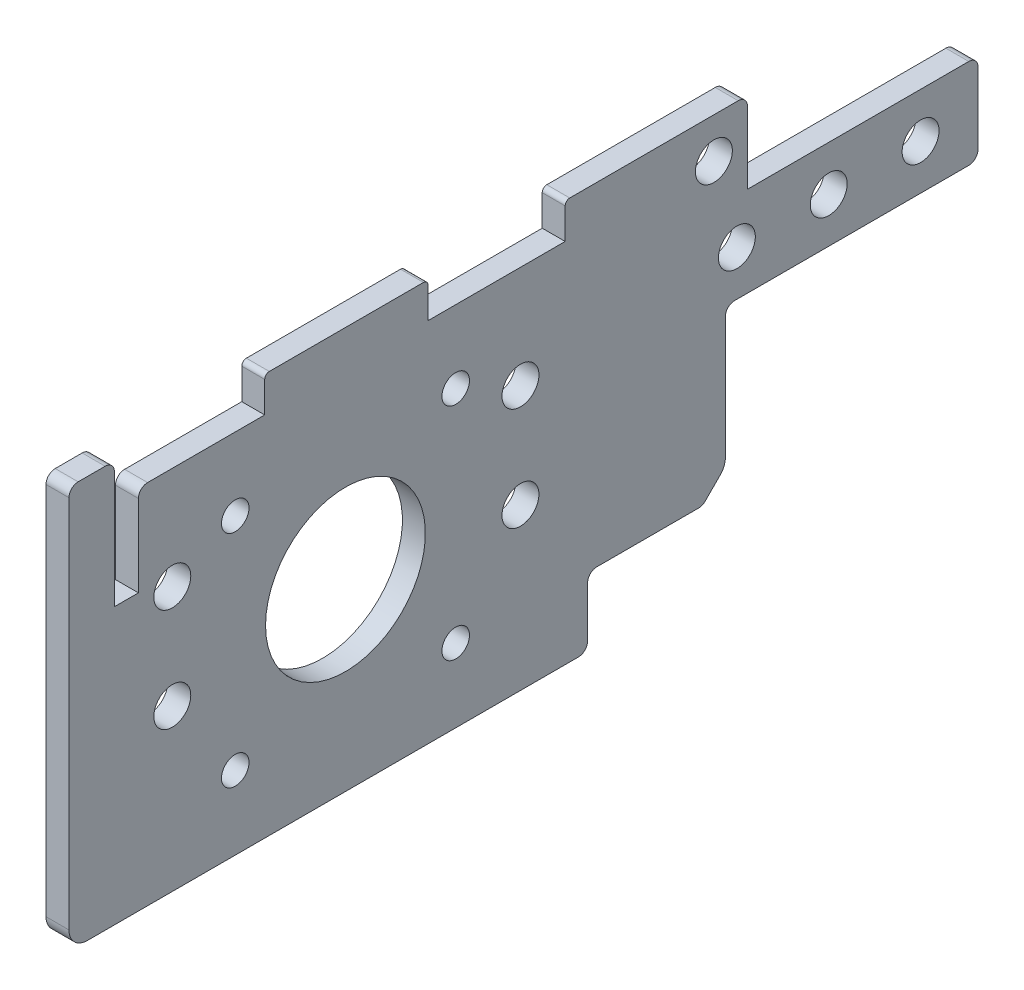
SolidWorks part; units mm, degrees
material "AISI Type A2 Tool Steel"
ref_plane "Front Plane" through (0, 0, 0) normal (0, 0, 1) x (1, 0, 0)
ref_plane "Top Plane" through (0, 0, 0) normal (0, 1, 0) x (1, 0, 0)
ref_plane "Right Plane" through (0, 0, 0) normal (1, 0, 0) x (0, 0, -1)
sketch "Top Layout" plane through (0, 0, 0) normal (0, 1, 0) x (1, 0, 0)
  line L0 (-114.046, -123.825) -> (-104.775, -123.825) construction
  line L1 (-104.775, -142.875) -> (-101.6, -142.875)
  line L2 (-104.775, -142.875) -> (-104.775, -104.775)
  line L3 (-104.775, -104.775) -> (-101.6, -104.775)
  line L4 (-101.6, -142.875) -> (-101.6, -104.775)
  line L5 (-104.775, -142.875) -> (-101.6, -104.775) construction
  line L6 (-104.775, -104.775) -> (-101.6, -142.875) construction
  line L7 (-19.05, -105.8164) -> (-101.6, -105.8164)
  line L8 (-19.05, -105.8164) -> (-19.05, -141.8336)
  line L9 (-19.05, -141.8336) -> (-101.6, -141.8336)
  line L10 (-101.6, -105.8164) -> (-101.6, -141.8336)
  line L11 (-19.05, -105.8164) -> (-101.6, -141.8336) construction
  line L12 (-19.05, -141.8336) -> (-101.6, -105.8164) construction
  line L13 (-133.096, -85.725) -> (-114.046, -85.725)
  line L14 (-133.096, -85.725) -> (-133.096, -161.925)
  line L15 (-133.096, -161.925) -> (-114.046, -161.925)
  line L16 (-114.046, -85.725) -> (-114.046, -161.925)
  line L17 (-133.096, -85.725) -> (-114.046, -161.925) construction
  line L18 (-133.096, -161.925) -> (-114.046, -85.725) construction
  line L19 (-104.775, -123.825) -> (0, -123.825) construction
  line L20 (0, -123.825) -> (0, 0) construction
  line L21 (-52.3528, -40.1717) -> (0, 0) construction
  line L22 (-70.6449, -16.3328) -> (-18.2922, 23.8388)
  line L23 (-34.0606, -64.0105) -> (18.2922, -23.8388)
  line L24 (-30.9251, 40.3023) -> (-122.2248, -29.7544)
  line L25 (-153.9748, -53.975) -> (-153.9748, -123.825)
  line L26 (-109.5248, -162.052) -> (109.5248, -162.052)
  line L27 (0, -162.052) -> (0, -123.825) construction
  line L28 (-109.5248, -162.052) -> (-109.5248, -20.0093) construction
  line L29 (-104.775, -142.875) -> (-104.775, -152.527)
  line L30 (-104.775, -152.527) -> (104.775, -152.527)
  line L31 (104.775, -104.775) -> (101.6, -104.775)
  line L32 (-144.4498, -73.025) -> (-109.5248, -73.025)
  line L33 (-144.4498, -73.025) -> (-144.4498, -123.825)
  line L34 (-144.4498, -123.825) -> (-109.5248, -123.825) construction
  line L35 (-109.5248, -73.025) -> (-109.5248, -162.052)
  line L36 (-144.4498, -73.025) -> (-109.5248, -123.825) construction
  line L37 (-144.4498, -123.825) -> (-109.5248, -73.025) construction
  line L38 (101.6, -142.875) -> (101.6, -104.775)
  line L39 (104.775, -142.875) -> (101.6, -142.875)
  line L40 (104.775, -142.875) -> (104.775, -104.775)
  line L41 (104.775, -142.875) -> (104.775, -152.527)
  line L42 (109.5248, -162.052) -> (109.5248, -20.0093) construction
  line L43 (30.9251, 40.3023) -> (122.2248, -29.7544)
  line L45 (19.05, -141.8336) -> (101.6, -141.8336)
  line L46 (101.6, -105.8164) -> (101.6, -141.8336)
  line L47 (19.05, -105.8164) -> (101.6, -105.8164)
  line L48 (19.05, -105.8164) -> (19.05, -141.8336)
  line L49 (133.096, -161.925) -> (114.046, -161.925)
  line L50 (114.046, -85.725) -> (114.046, -161.925)
  line L51 (133.096, -85.725) -> (114.046, -85.725)
  line L52 (133.096, -85.725) -> (133.096, -161.925)
  line L53 (144.4498, -123.825) -> (109.5248, -123.825) construction
  line L54 (109.5248, -73.025) -> (109.5248, -162.052)
  line L55 (144.4498, -73.025) -> (109.5248, -73.025)
  line L56 (144.4498, -73.025) -> (144.4498, -123.825)
  line L57 (-109.5248, -123.825) -> (-109.5248, -162.052) construction
  line L62 (-153.9748, -53.975) -> (-122.2248, -53.975)
  line L63 (-122.2248, -53.975) -> (-122.2248, -29.7544)
  line L64 (-144.4498, -123.825) -> (-153.9748, -123.825)
  line L65 (153.9748, -53.975) -> (153.9748, -123.825)
  line L66 (109.5248, -123.825) -> (109.5248, -162.052) construction
  line L67 (144.4498, -123.825) -> (153.9748, -123.825)
  line L68 (122.2248, -29.7544) -> (122.2248, -53.975)
  line L73 (-104.775, -104.775) -> (-104.775, -16.3647) construction
  line L74 (-95.25, -162.052) -> (-95.25, -9.0559) construction
  line L75 (-109.5248, -162.052) -> (-109.5248, -123.825) construction
  line L76 (109.5248, -162.052) -> (109.5248, -123.825) construction
  line L77 (122.2248, -53.975) -> (153.9748, -53.975)
  line L83 (104.775, -155.5496) -> (-104.775, -155.5496) construction
  line L88 (95.25, -162.052) -> (95.25, -9.0559) construction
  line L89 (104.775, -104.775) -> (104.775, -16.3647) construction
  line L92 (-104.775, -152.527) -> (-104.775, -162.052) construction
  line L93 (-14.605, -76.327) -> (14.605, -76.327)
  line L94 (-14.605, -76.327) -> (-14.605, -152.527)
  line L95 (-14.605, -152.527) -> (14.605, -152.527)
  line L96 (14.605, -76.327) -> (14.605, -152.527)
  line L97 (-14.605, -76.327) -> (14.605, -152.527) construction
  line L98 (-14.605, -152.527) -> (14.605, -76.327) construction
  line L99 (104.775, -152.527) -> (104.775, -162.052) construction
  line L100 (-19.05, -105.8164) -> (0, -105.8164) construction
  line L107 (0, -105.8164) -> (19.05, -105.8164) construction
  line L108 (104.775, -123.825) -> (114.046, -123.825) construction
  circle A0 centre (0, 0) radius 114.3
  circle A1 centre (0, 0) radius 6.35
  circle A2 centre (-52.3528, -40.1717) radius 17.8
  circle A3 centre (0, 0) radius 30.0482
  circle A4 centre (-52.3528, -40.1717) radius 30.0482
  arc A5 (-30.9251, 40.3023) -> (30.9251, 40.3023) centre (0, 0) cw
  point P2 (-103.1875, -123.825)
  point P7 (-60.325, -123.825)
  point P12 (-123.571, -123.825)
  point P30 (-126.9873, -98.425)
  point P35 (0, -114.427)
  point P53 (0, -152.527)
  dimension "D1" = 35.6
  dimension "D2" = 12.7
  dimension "D3" = 228.6
  dimension "D11" = 60.0964
  dimension "D12" = 50.8
  dimension "D14" = 52.5
  dimension "D4" = 3.175
  dimension "D5" = 19.05
  dimension "D6" = 76.2
  dimension "D7" = 82.55
  dimension "D8" = 38.1
  dimension "D9" = 104.775
  dimension "D10" = 18.0086
  dimension "D13" = 9.525
  dimension "D15" = 4.7498
  dimension "D16" = 9.525
  dimension "D17" = 9.652
  dimension "D18" = 50.8
  dimension "D19" = 12.446
  dimension "D20" = 65.9892
  dimension "D21" = 19.05
  dimension "D22" = 34.925
  dimension "D23" = 123.825
  dimension "D24" = 12.7
  dimension "D25" = 9.525
  dimension "D26" = 29.21
  dimension "D27" = 76.2
  dimension "D28" = 3.0226
sketch "Side Layout" plane through (0, 0, 0) normal (1, 0, 0) x (0, 0, -1)
  line L0 (0, -38.1) -> (0, 33.7344) construction
  line L1 (-114.3, -20.955) -> (114.3, -20.955)
  line L2 (-114.3, -20.955) -> (-114.3, -33.655)
  line L3 (-114.3, -33.655) -> (114.3, -33.655)
  line L4 (114.3, -20.955) -> (114.3, -33.655)
  line L5 (-114.3, -20.955) -> (114.3, -33.655) construction
  line L6 (-114.3, -33.655) -> (114.3, -20.955) construction
  line L7 (-9.525, -32.9406) -> (9.525, -32.9406)
  line L8 (-9.525, -32.9406) -> (-9.525, -38.1)
  line L9 (-9.525, -38.1) -> (9.525, -38.1)
  line L10 (9.525, -32.9406) -> (9.525, -38.1)
  line L11 (-9.525, -32.9406) -> (9.525, -38.1) construction
  line L12 (-9.525, -38.1) -> (9.525, -32.9406) construction
  line L13 (-11.9126, -29.3338) -> (11.9126, -29.3338)
  line L14 (-11.9126, -29.3338) -> (-11.9126, -32.9406)
  line L15 (-11.9126, -32.9406) -> (11.9126, -32.9406)
  line L16 (11.9126, -29.3338) -> (11.9126, -32.9406)
  line L17 (-11.9126, -29.3338) -> (11.9126, -32.9406) construction
  line L18 (-11.9126, -32.9406) -> (11.9126, -29.3338) construction
  line L19 (-6.35, -32.9406) -> (6.35, -32.9406)
  line L20 (-6.35, -32.9406) -> (-6.35, 33.7344)
  line L21 (-6.35, 33.7344) -> (6.35, 33.7344)
  line L22 (6.35, -32.9406) -> (6.35, 33.7344)
  line L23 (-6.35, -32.9406) -> (6.35, 33.7344) construction
  line L24 (-6.35, 33.7344) -> (6.35, -32.9406) construction
  line L25 (-162.052, 0) -> (-123.825, 0) construction
  line L26 (114.3, -33.655) -> (114.3, 0) construction
  line L27 (-142.875, 19.05) -> (-104.775, 19.05)
  line L28 (-40.1717, -9.525) -> (-40.1717, 5.4) construction
  line L29 (-142.875, 19.05) -> (-142.875, -19.05)
  line L30 (-142.875, -19.05) -> (-104.775, -19.05)
  line L31 (-104.775, 19.05) -> (-104.775, -19.05)
  line L32 (-142.875, 19.05) -> (-104.775, -19.05) construction
  line L33 (-142.875, -19.05) -> (-104.775, 19.05) construction
  line L34 (-130.175, -38.1) -> (-117.9516, -38.1) construction
  line L35 (-57.9717, -14.6) -> (-22.3717, -14.6)
  line L36 (-30.0482, -2.794) -> (30.0482, -2.794)
  line L37 (-30.0482, -2.794) -> (-30.0482, -20.955)
  line L38 (-30.0482, -20.955) -> (30.0482, -20.955)
  line L39 (30.0482, -2.794) -> (30.0482, -20.955)
  line L40 (-30.0482, -2.794) -> (30.0482, -20.955) construction
  line L41 (-30.0482, -20.955) -> (30.0482, -2.794) construction
  line L42 (-30.0482, -2.794) -> (-30.0482, 0) construction
  line L43 (-123.825, 0) -> (0, 0) construction
  line L44 (-57.9717, -14.6) -> (-57.9717, 25.4)
  line L45 (-57.9717, 25.4) -> (-22.3717, 25.4)
  line L46 (-22.3717, -14.6) -> (-22.3717, 25.4)
  line L47 (-19.05, 0) -> (19.05, 0)
  line L48 (-19.05, 0) -> (-19.05, -1.9812)
  line L49 (-19.05, -1.9812) -> (19.05, -1.9812)
  line L50 (19.05, 0) -> (19.05, -1.9812)
  line L51 (-19.05, 0) -> (19.05, -1.9812) construction
  line L52 (-19.05, -1.9812) -> (19.05, 0) construction
  line L53 (-70.2199, -3.175) -> (-10.1235, -3.175)
  line L54 (-70.2199, -3.175) -> (-70.2199, -15.875)
  line L55 (-70.2199, -15.875) -> (-10.1235, -15.875)
  line L56 (-10.1235, -3.175) -> (-10.1235, -15.875)
  line L57 (-70.2199, -3.175) -> (-10.1235, -15.875) construction
  line L58 (-70.2199, -15.875) -> (-10.1235, -3.175) construction
  line L59 (-40.1717, -9.525) -> (-40.1717, 0) construction
  line L60 (-57.9717, -14.6) -> (-22.3717, 25.4) construction
  line L61 (-57.9717, 25.4) -> (-22.3717, -14.6) construction
  line L62 (-22.3717, 0) -> (-57.9717, 0) construction
  line L63 (-137.8162, 0) -> (-123.825, -13.9912) construction
  line L64 (-139.065, 15.24) -> (-108.585, 15.24) construction
  line L65 (-139.065, 15.24) -> (-139.065, -15.24) construction
  line L66 (-139.065, -15.24) -> (-108.585, -15.24) construction
  line L67 (-108.585, 15.24) -> (-108.585, -15.24) construction
  line L68 (-139.065, 15.24) -> (-108.585, -15.24) construction
  line L69 (-139.065, -15.24) -> (-108.585, 15.24) construction
  line L70 (-137.8162, 0) -> (-123.825, 13.9912) construction
  line L71 (-123.825, -13.9912) -> (-109.8338, 0) construction
  line L72 (-123.825, 13.9912) -> (-109.8338, 0) construction
  line L73 (-137.8162, 0) -> (-109.8338, 0) construction
  line L74 (-123.825, -13.9912) -> (-123.825, 13.9912) construction
  line L75 (-6.35, 17.8594) -> (6.35, 17.8594)
  line L76 (114.3, 0) -> (-114.3, 0) construction
  line L77 (-22.3717, 19.05) -> (-6.35, 19.05) construction
  line L78 (-123.825, 38.1) -> (-97.9206, 38.1) construction
  line L79 (-19.05, -3.5814) -> (19.05, -3.5814)
  line L80 (-19.05, -3.5814) -> (-19.05, -1.9812)
  line L81 (-19.05, -1.9812) -> (19.05, -1.9812)
  line L82 (19.05, -3.5814) -> (19.05, -1.9812)
  line L83 (-19.05, -3.5814) -> (19.05, -1.9812) construction
  line L84 (-19.05, -1.9812) -> (19.05, -3.5814) construction
  line L85 (-8.7376, -16.7608) -> (8.7376, -16.7608)
  line L86 (-8.7376, -16.7608) -> (-8.7376, -29.3338)
  line L87 (-8.7376, -29.3338) -> (8.7376, -29.3338)
  line L88 (8.7376, -16.7608) -> (8.7376, -29.3338)
  line L89 (-8.7376, -16.7608) -> (8.7376, -29.3338) construction
  line L90 (-8.7376, -29.3338) -> (8.7376, -16.7608) construction
  line L91 (-8.7376, -3.5814) -> (8.7376, -3.5814)
  line L92 (-8.7376, -3.5814) -> (-8.7376, -16.1544)
  line L93 (-8.7376, -16.1544) -> (8.7376, -16.1544)
  line L94 (8.7376, -3.5814) -> (8.7376, -16.1544)
  line L95 (-8.7376, -3.5814) -> (8.7376, -16.1544) construction
  line L96 (-8.7376, -16.1544) -> (8.7376, -3.5814) construction
  circle A0 centre (-123.825, 0) radius 18.0086
  circle A1 centre (-123.825, 0) radius 38.1
  circle A2 centre (-139.065, 15.24) radius 1.905
  circle A3 centre (-108.585, 15.24) radius 1.905
  circle A4 centre (-108.585, -15.24) radius 1.905
  circle A5 centre (-139.065, -15.24) radius 1.905
  circle A6 centre (-137.8162, 0) radius 1.6002
  circle A7 centre (-123.825, 13.9912) radius 1.6002
  circle A8 centre (-109.8338, 0) radius 1.6002
  circle A9 centre (-123.825, -13.9912) radius 1.6002
  point P0 (0, -27.305)
  point P6 (0, -31.1372)
  point P7 (0, -35.5203)
  point P21 (0, 0.3969)
  point P32 (0, -11.8745)
  point P43 (0, -0.9906)
  point P55 (-40.1717, -9.525)
  point P72 (-40.1717, 5.4)
  point P88 (0, -23.0473)
  point P93 (0, -2.7813)
  point P102 (0, -9.8679)
  dimension "D17" = 3.81
  dimension "D18" = 3.2004
  dimension "D1" = 12.7
  dimension "D2" = 5.1594
  dimension "D3" = 19.05
  dimension "D4" = 3.6068
  dimension "D5" = 23.8252
  dimension "D6" = 12.7
  dimension "D7" = 18.161
  dimension "D8" = 1.9812
  dimension "D9" = 12.7
  dimension "D10" = 40
  dimension "D11" = 25.4
  dimension "D12" = 50.8
  dimension "D13" = 41.275
  dimension "D14" = 30.48
  dimension "D15" = 4.445
  dimension "D16" = 19.7866
  dimension "D19" = 15.875
  dimension "D20" = 6.35
  dimension "D21" = 38.1
  dimension "D22" = 1.6002
  dimension "D23" = 38.1
  dimension "D24" = 17.4752
  dimension "D25" = 12.573
ref_plane "Plane1" through (0, 25.4, 0) normal (0, 1, 0) x (1, 0, 0)
sketch "Sketch3" plane through (0, 25.4, 0) normal (0, 1, 0) x (1, 0, 0)
  line L0 (-104.775, -36.3747) -> (-30.9251, 20.2924)
  line L1 (-104.775, -104.775) -> (-104.775, -16.3647) construction
  line L2 (0, -200130.175) -> (0, 199882.0484) construction
  line L3 (-30.9251, 40.3023) -> (-122.2248, -29.7544) construction
  line L5 (-104.775, -36.3747) -> (-104.775, -77.6497)
  line L6 (-92.075, -77.6497) -> (-104.775, -77.6497)
  line L7 (30.9251, 20.2924) -> (104.775, -36.3747)
  line L8 (104.775, -77.6497) -> (92.075, -77.6497)
  line L9 (104.775, -36.3747) -> (104.775, -77.6497)
  line L11 (104.775, -104.775) -> (104.775, -16.3647) construction
  line L12 (30.9251, 40.3023) -> (122.2248, -29.7544) construction
  line L13 (92.075, -74.6536) -> (24.1423, -22.5271)
  line L14 (-32.2514, -66.3682) -> (20.1013, -26.1965)
  line L15 (-30.9251, 20.2924) -> (0, 44.022)
  line L16 (0, 44.022) -> (30.9251, 20.2924)
  line L17 (-92.075, -77.6497) -> (-92.075, -73.1917)
  line L19 (-92.075, -73.1917) -> (-52.3528, -73.1917)
  line L20 (92.075, -74.6536) -> (92.075, -77.6497)
  circle A0 centre (-52.3528, -40.1717) radius 17.8 construction
  circle A1 centre (-52.3528, -40.1717) radius 17.8
  circle A2 centre (0, 0) radius 6.35
  circle A3 centre (0, 0) radius 6.35 construction
  arc A4 (-52.3528, -73.1917) -> (-32.2514, -66.3682) centre (-52.3528, -40.1717) ccw
  arc A5 (20.1013, -26.1965) -> (24.1423, -22.5271) centre (0, 0) ccw
  arc A6 (30.9251, 20.2924) -> (-30.9251, 20.2924) centre (0, -20.01) ccw construction
  point P28 (0, 44.022)
  dimension "D1" = 33.02
  dimension "D5" = 50.8
  dimension "D2" = 41.275
  dimension "D3" = 34.925
  dimension "D4" = 12.7
  dimension "D6" = 38.1
ref_plane "Plane3" through (-104.775, 0, 0) normal (-1, 0, 0) x (0, 0, 1)
sketch "Sketch6" plane through (-104.775, 0, 0) normal (-1, 0, 0) x (0, 0, 1)
  line L0 (162.052, -25.4) -> (162.052, 25.4)
  line L1 (162.052, 25.4) -> (77.6497, 25.4)
  line L2 (36.3747, 25.4) -> (77.6497, 25.4) construction
  line L3 (147.7645, 11.1125) -> (162.052, 11.1125) construction
  line L4 (162.052, 0) -> (71.2997, 0) construction
  line L5 (77.6497, 25.4) -> (77.6497, 19.05)
  line L6 (77.6497, 19.05) -> (36.3747, 19.05)
  line L7 (36.3747, 19.05) -> (36.3747, 6.35)
  line L8 (36.3747, 6.35) -> (71.2997, 6.35)
  line L10 (99.6315, -3.175) -> (99.6315, 11.1125) construction
  line L11 (71.2997, -25.4) -> (162.052, -25.4)
  line L13 (71.2997, 6.35) -> (71.2997, -25.4)
  line L14 (152.527, -25.4) -> (152.527, 25.4) construction
  line L15 (99.6315, 11.1125) -> (99.6315, 25.4) construction
  line L16 (147.7645, 11.1125) -> (147.7645, 25.4) construction
  line L17 (94.869, -7.9375) -> (104.394, -7.9375) construction
  line L18 (94.869, -7.9375) -> (94.869, 25.4) construction
  line L19 (94.869, 25.4) -> (104.394, 25.4) construction
  line L20 (104.394, -7.9375) -> (104.394, 25.4) construction
  line L21 (94.869, -7.9375) -> (104.394, 25.4) construction
  line L22 (94.869, 25.4) -> (104.394, -7.9375) construction
  line L23 (147.7645, 11.1125) -> (147.7645, -3.175) construction
  line L24 (104.394, -7.9375) -> (123.825, -7.9375) construction
  line L25 (143.002, -7.9375) -> (152.527, -7.9375) construction
  line L26 (143.002, -7.9375) -> (143.002, 25.4) construction
  line L27 (143.002, 25.4) -> (152.527, 25.4) construction
  line L28 (152.527, -7.9375) -> (152.527, 25.4) construction
  line L29 (143.002, -7.9375) -> (152.527, 25.4) construction
  line L30 (143.002, 25.4) -> (152.527, -7.9375) construction
  line L31 (123.825, -7.9375) -> (152.527, -7.9375) construction
  line L32 (104.775, 19.05) -> (104.775, -19.05) construction
  line L34 (155.702, -25.4) -> (155.702, 25.4) construction
  circle A0 centre (109.8338, 0) radius 1.6002 construction
  circle A1 centre (123.825, 13.9912) radius 1.6002 construction
  circle A2 centre (137.8162, 0) radius 1.6002 construction
  circle A3 centre (123.825, -13.9912) radius 1.6002 construction
  circle A4 centre (109.8338, 0) radius 1.6002 construction
  circle A5 centre (123.825, 13.9912) radius 1.6002 construction
  circle A6 centre (137.8162, 0) radius 1.6002 construction
  circle A7 centre (123.825, -13.9912) radius 1.6002 construction
  circle A8 centre (123.825, 0) radius 18.0086 construction
  circle A9 centre (123.825, 0) radius 18.0086 construction
  circle A10 centre (123.825, 0) radius 9.525
  circle A11 centre (108.585, -15.24) radius 1.905 construction
  circle A12 centre (108.585, 15.24) radius 1.905 construction
  circle A13 centre (139.065, 15.24) radius 1.905 construction
  circle A14 centre (139.065, -15.24) radius 1.905 construction
  circle A15 centre (108.585, -15.24) radius 1.905
  circle A16 centre (108.585, 15.24) radius 1.905
  circle A17 centre (139.065, 15.24) radius 1.905
  circle A18 centre (139.065, -15.24) radius 1.905
  circle A19 centre (147.7645, 11.1125) radius 2.5527
  circle A26 centre (99.6315, 11.1125) radius 2.5527
  circle A27 centre (99.6315, -3.175) radius 2.5527
  circle A28 centre (147.7645, -3.175) radius 2.5527
  point P29 (0, 0)
  point P55 (99.6315, 8.7312)
  point P61 (147.7645, 8.7312)
  dimension "D4" = 19.05
  dimension "D7" = 5.1054
  dimension "D1" = 6.35
  dimension "D2" = 12.7
  dimension "D3" = 25.4
  dimension "D5" = 6.35
  dimension "D6" = 3.175
  dimension "D8" = 0.381
  dimension "D9" = 14.2875
  dimension "D10" = 9.525
  dimension "D12" = 33.3375
extrude "Side Plate Extrude" add sketch "Sketch6" along normal up to vertex (4.7498 mm away) up to point (-109.5248, 0, 73.025)
sketch "Sketch12" [suppressed] plane through (0, 19.05, 0) normal (0, 1, 0) x (1, 0, 0)
  line L0 (-104.775, -77.6497) -> (-104.775, -36.3747)
  line L1 (-104.775, -36.3747) -> (-92.075, -36.3747)
  line L3 (-92.075, -36.3747) -> (-92.075, -77.6497)
  line L5 (-92.075, -77.6497) -> (-104.775, -77.6497)
  line L6 (-98.425, -77.6497) -> (-98.425, -63.3622) construction
  line L7 (-98.425, -63.3622) -> (-98.425, -50.6622) construction
  line L8 (-98.425, -50.6622) -> (-98.425, -36.3747) construction
  line L10 (-98.425, -36.3747) -> (-104.775, -36.3747) construction
  circle A0 centre (-98.425, -63.3622) radius 2.5527
  circle A1 centre (-98.425, -50.6622) radius 2.5527
  dimension "D2" = 5.1054
  dimension "D1" = 12.7
  dimension "D3" = 12.7
sketch "Sketch15" plane through (-109.5248, 0, 0) normal (-1, 0, 0) x (0, 0, 1)
  line L0 (36.3747, 12.7) -> (44.3122, 12.7) construction
  line L1 (36.3747, 19.05) -> (36.3747, 6.35) construction
  line L2 (44.3122, 12.7) -> (57.0122, 12.7) construction
  line L3 (57.0122, 12.7) -> (69.7122, 12.7) construction
  line L4 (69.7122, 12.7) -> (77.6497, 12.7) construction
  line L5 (77.6497, 12.7) -> (77.6497, 19.05) construction
  circle A0 centre (44.3122, 12.7) radius 2.5527
  circle A1 centre (57.0122, 12.7) radius 2.5527
  circle A2 centre (69.7122, 12.7) radius 2.5527
  dimension "D1" = 5.1054
  dimension "D2" = 12.7
extrude "Custom Nutstrip Holes" cut sketch "Sketch15" against normal through all
ref_plane "Plane5" through (0, 0, 152.527) normal (0, 0, 1) x (1, 0, 0)
sketch "Sketch41" plane through (0, 0, 152.527) normal (0, 0, 1) x (1, 0, 0)
  line L0 (-104.775, -7.9375) -> (-104.775, 25.4) construction
  line L1 (-104.775, -7.9375) -> (-104.775, 12.7)
  line L2 (-104.775, -7.9375) -> (104.775, -7.9375)
  line L3 (104.775, -7.9375) -> (104.775, 12.7)
  line L4 (104.775, 25.4) -> (-104.775, 25.4)
  line L5 (0, -7.9375) -> (0, 25.4) construction
  line L6 (-104.775, 3.9624) -> (-100.0125, 3.9624) construction
  line L7 (-100.0125, 3.9624) -> (-100.0125, 25.4) construction
  line L8 (104.775, 3.9624) -> (100.0125, 3.9624) construction
  line L9 (100.0125, 3.9624) -> (100.0125, 25.4) construction
  line L10 (19.05, 20.6375) -> (23.8252, 20.6375) construction
  line L11 (19.05, 15.875) -> (78.5876, 15.875) construction
  line L12 (19.05, 15.875) -> (19.05, 25.4) construction
  line L13 (19.05, 25.4) -> (78.5876, 25.4) construction
  line L14 (78.5876, 15.875) -> (78.5876, 25.4) construction
  line L15 (19.05, 15.875) -> (78.5876, 25.4) construction
  line L16 (19.05, 25.4) -> (78.5876, 15.875) construction
  line L17 (23.8252, 20.6375) -> (38.1127, 20.6375) construction
  line L18 (38.1127, 20.6375) -> (52.4002, 20.6375) construction
  line L19 (52.4002, 20.6375) -> (66.6877, 20.6375) construction
  line L20 (-104.775, 25.4) -> (-112.395, 25.4)
  line L21 (-112.395, 25.4) -> (-112.395, 3.175)
  line L22 (-112.395, 3.175) -> (-109.5248, 3.175)
  line L23 (-109.5248, 3.175) -> (-109.5248, 12.7)
  line L24 (-109.5248, 12.7) -> (-104.775, 12.7)
  line L25 (-104.775, 12.7) -> (-104.775, 25.4) construction
  line L26 (104.775, 25.4) -> (112.395, 25.4)
  line L27 (112.395, 25.4) -> (112.395, 3.175)
  line L28 (112.395, 3.175) -> (109.5248, 3.175)
  line L29 (109.5248, 3.175) -> (109.5248, 12.7)
  line L30 (109.5248, 12.7) -> (104.775, 12.7)
  line L31 (104.775, 12.7) -> (104.775, 25.4) construction
  line L32 (-100.0125, 3.9624) -> (-87.3125, 3.9624) construction
  line L33 (-63.5, -1.5875) -> (0, -1.5875) construction
  line L34 (0, -1.5875) -> (63.5, -1.5875) construction
  line L35 (63.5, -1.5875) -> (63.5, -7.9375) construction
  circle A0 centre (-100.0125, 3.9624) radius 2.5527
  circle A1 centre (100.0125, 3.9624) radius 2.5527
  circle A2 centre (23.8252, 20.6375) radius 2.5527
  circle A3 centre (38.1127, 20.6375) radius 2.5527
  circle A4 centre (52.4002, 20.6375) radius 2.5527
  circle A5 centre (66.6877, 20.6375) radius 2.5527
  circle A6 centre (-66.6877, 20.6375) radius 2.5527
  circle A7 centre (-52.4002, 20.6375) radius 2.5527
  circle A8 centre (-38.1127, 20.6375) radius 2.5527
  circle A9 centre (-23.8252, 20.6375) radius 2.5527
  circle A10 centre (-87.3125, 3.9624) radius 2.5527
  circle A11 centre (87.3125, 3.9624) radius 2.5527
  circle A12 centre (-63.5, -1.5875) radius 2.5527
  circle A13 centre (63.5, -1.5875) radius 2.5527
  point P14 (48.8188, 20.6375)
  dimension "D3" = 5.1054
  dimension "D7" = 5.1054
  dimension "D1" = 21.4376
  dimension "D2" = 4.7625
  dimension "D4" = 9.525
  dimension "D5" = 59.5376
  dimension "D6" = 4.7752
  dimension "D8" = 14.2875
  dimension "D9" = 7.62
  dimension "D10" = 4.7498
  dimension "D11" = 12.7
  dimension "D12" = 9.525
  dimension "D13" = 19.05
  dimension "D14" = 12.7
  dimension "D15" = 6.35
  dimension "D16" = 63.5
sketch "Sketch43" plane through (-109.5248, 0, 0) normal (-1, 0, 0) x (0, 0, 1)
  line L1 (152.527, 12.7) -> (155.702, 12.7)
  line L2 (152.527, 12.7) -> (152.527, 25.4)
  line L3 (152.527, 25.4) -> (155.702, 25.4)
  line L4 (155.702, 12.7) -> (155.702, 25.4)
  line L5 (152.527, 12.7) -> (155.702, 25.4) construction
  line L6 (152.527, 25.4) -> (155.702, 12.7) construction
  line L7 (162.052, 25.4) -> (77.6497, 25.4) construction
  point P4 (154.1145, 19.05)
  dimension "D1" = 3.175
extrude "Cut-Extrude19" cut sketch "Sketch43" against normal through all
sketch "Sketch44" plane through (0, 25.4, 0) normal (0, 1, 0) x (1, 0, 0)
  line L0 (73.8315, -147.7645) -> (73.8315, -152.527) construction
  line L1 (92.075, -74.6536) -> (92.075, -77.6497) construction
  line L2 (-92.075, -77.6497) -> (-92.075, -73.1917) construction
  line L3 (0, -123.825) -> (0, 0) construction
  line L4 (-92.075, -73.1917) -> (-52.3528, -73.1917) construction
  line L5 (-104.775, -104.775) -> (-104.775, -16.3647) construction
  line L6 (-32.2514, -66.3682) -> (20.1013, -26.1965) construction
  line L21 (-104.775, -68.1247) -> (-104.775, -152.527)
  line L22 (-104.775, -152.527) -> (104.775, -152.527)
  line L23 (104.775, -152.527) -> (104.775, -68.1247)
  line L34 (-104.775, -99.6315) -> (-100.0125, -99.6315) construction
  line L35 (-104.775, -147.7645) -> (-100.0125, -147.7645) construction
  line L36 (0, -152.527) -> (0, -35.6178) construction
  line L38 (30.969, -147.7645) -> (45.2565, -147.7645) construction
  line L39 (45.2565, -147.7645) -> (59.544, -147.7645) construction
  line L40 (59.544, -147.7645) -> (73.8315, -147.7645) construction
  line L41 (23.8252, -152.527) -> (30.969, -152.527) construction
  line L42 (104.775, -152.527) -> (-104.775, -152.527) construction
  line L43 (30.969, -152.527) -> (38.1127, -152.527) construction
  line L44 (30.969, -152.527) -> (30.969, -147.7645) construction
  line L45 (-92.075, -77.6497) -> (-104.775, -77.6497) construction
  line L48 (-35.1507, -62.5899) -> (-8.9743, -42.504) construction
  line L49 (-8.9743, -42.504) -> (17.2021, -22.4182) construction
  line L50 (45.5313, -32.9364) -> (87.3125, -64.9962) construction
  line L51 (92.075, -74.6536) -> (24.1423, -22.5271) construction
  line L52 (104.775, -77.6497) -> (92.075, -77.6497) construction
  line L79 (-104.775, -68.1247) -> (-92.075, -68.1247)
  line L80 (-92.075, -68.1247) -> (-92.075, -63.6667)
  line L85 (21.8118, -8.7328) -> (92.075, -62.6476)
  line L86 (-38.0499, -58.8115) -> (14.3028, -18.6398)
  line L87 (-92.075, -63.6667) -> (-52.3528, -63.6667)
  line L88 (92.075, -62.6476) -> (92.075, -68.1247)
  line L89 (92.075, -68.1247) -> (104.775, -68.1247)
  circle A0 centre (-73.8315, -147.7645) radius 2.5527
  circle A1 centre (-59.544, -147.7645) radius 2.5527
  circle A2 centre (-45.2565, -147.7645) radius 2.5527
  circle A3 centre (-30.969, -147.7645) radius 2.5527
  circle A17 centre (-100.0125, -99.6315) radius 2.5527
  circle A18 centre (-100.0125, -147.7645) radius 2.5527
  circle A19 centre (100.0125, -147.7645) radius 2.5527
  circle A20 centre (100.0125, -99.6315) radius 2.5527
  circle A21 centre (30.969, -147.7645) radius 2.5527
  circle A22 centre (45.2565, -147.7645) radius 2.5527
  circle A23 centre (59.544, -147.7645) radius 2.5527
  circle A24 centre (73.8315, -147.7645) radius 2.5527
  circle A25 centre (-87.3125, -68.4292) radius 4.7625 construction
  circle A26 centre (-35.1507, -62.5899) radius 4.7625 construction
  circle A27 centre (-8.9743, -42.504) radius 4.7625 construction
  circle A28 centre (17.2021, -22.4182) radius 4.7625 construction
  circle A29 centre (45.5313, -32.9364) radius 4.7625 construction
  circle A30 centre (87.3125, -64.9962) radius 4.7625 construction
  circle A32 centre (-87.3125, -68.4292) radius 2.5527
  circle A33 centre (-35.1507, -62.5899) radius 2.5527
  circle A34 centre (-8.9743, -42.504) radius 2.5527 construction
  circle A35 centre (17.2021, -22.4182) radius 2.5527
  circle A36 centre (45.5313, -32.9364) radius 2.5527
  circle A37 centre (87.3125, -64.9962) radius 2.5527
  circle A38 centre (-97.155, -85.2697) radius 7.62 construction
  circle A39 centre (97.155, -85.2697) radius 7.62 construction
  circle A40 centre (24.5121, -32.4156) radius 7.62 construction
  arc A41 (20.1013, -26.1965) -> (24.1423, -22.5271) centre (0, 0) ccw construction
  circle A42 centre (-97.155, -85.2697) radius 2.5527
  circle A43 centre (24.5121, -32.4156) radius 2.5527
  circle A44 centre (97.155, -85.2697) radius 2.5527
  arc A56 (14.3028, -18.6398) -> (21.8118, -8.7328) centre (0, 0) ccw
  arc A57 (-52.3528, -63.6667) -> (-38.0499, -58.8115) centre (-52.3528, -40.1717) ccw
  point P4 (-104.775, -152.527)
  dimension "D2" = 5.1054
  dimension "D7" = 5.1054
  dimension "D8" = 15.24
  dimension "D3" = 9.525
  dimension "D9" = 9.525
  dimension "D4" = 4.7625
  dimension "D5" = 14.2875
  dimension "D6" = 9.525
  dimension "D1" = 4.7625
  dimension "D10" = 52.664
sketch "Sketch72" plane through (0, 25.4, 0) normal (0, 1, 0) x (1, 0, 0)
  line L0 (-104.775, -68.1247) -> (-104.775, -152.527) construction
  line L1 (-104.775, -152.527) -> (-109.5248, -152.527)
  line L2 (-104.775, -152.527) -> (-104.775, -135.0645)
  line L3 (-104.775, -135.0645) -> (-109.5248, -135.0645)
  line L4 (-109.5248, -152.527) -> (-109.5248, -135.0645)
  line L5 (-104.775, -152.527) -> (-109.5248, -135.0645) construction
  line L6 (-104.775, -135.0645) -> (-109.5248, -152.527) construction
  line L7 (-104.775, -152.527) -> (104.775, -152.527) construction
  line L8 (-77.0065, -152.527) -> (-73.8315, -147.7645) construction
  line L9 (-77.0065, -152.527) -> (-27.794, -152.527)
  line L10 (-77.0065, -152.527) -> (-77.0065, -155.5496)
  line L11 (-77.0065, -155.5496) -> (-27.794, -155.5496)
  line L12 (-27.794, -152.527) -> (-27.794, -155.5496)
  line L13 (-77.0065, -152.527) -> (-27.794, -155.5496) construction
  line L14 (-77.0065, -155.5496) -> (-27.794, -152.527) construction
  line L15 (-27.794, -152.527) -> (-30.969, -147.7645) construction
  line L16 (-77.0065, -152.527) -> (-77.0065, -147.7645) construction
  line L18 (-104.775, -93.5247) -> (-109.5248, -93.5247)
  line L19 (-104.775, -93.5247) -> (-104.775, -112.3315)
  line L20 (-104.775, -112.3315) -> (-109.5248, -112.3315)
  line L21 (-109.5248, -93.5247) -> (-109.5248, -112.3315)
  line L22 (-104.775, -93.5247) -> (-109.5248, -112.3315) construction
  line L23 (-104.775, -112.3315) -> (-109.5248, -93.5247) construction
  line L24 (0, -152.527) -> (-12.7, -152.527)
  line L25 (0, -152.527) -> (0, -155.5496)
  line L26 (0, -155.5496) -> (-12.7, -155.5496)
  line L27 (-12.7, -152.527) -> (-12.7, -155.5496)
  line L28 (0, -152.527) -> (-12.7, -155.5496) construction
  line L29 (0, -155.5496) -> (-12.7, -152.527) construction
  line L30 (-104.775, -68.1247) -> (-109.5248, -68.1247)
  line L31 (-104.775, -68.1247) -> (-104.775, -77.6497)
  line L32 (-104.775, -77.6497) -> (-109.5248, -77.6497)
  line L33 (-109.5248, -68.1247) -> (-109.5248, -77.6497)
  line L34 (-104.775, -68.1247) -> (-109.5248, -77.6497) construction
  line L35 (-104.775, -77.6497) -> (-109.5248, -68.1247) construction
  line L38 (-103.505, -155.5496) -> (-90.805, -155.5496)
  line L39 (-90.805, -152.527) -> (-90.805, -155.5496)
  line L40 (-103.505, -155.5496) -> (-103.505, -152.527)
  line L41 (-103.505, -155.5496) -> (-90.805, -152.527) construction
  line L42 (-103.505, -152.527) -> (-90.805, -152.527)
  line L43 (-77.0065, -147.7645) -> (-73.8315, -147.7645) construction
  line L44 (-103.505, -152.527) -> (-101.5221, -149.823) construction
  circle A0 centre (-100.0125, -147.7645) radius 2.5527 construction
  circle A1 centre (-73.8315, -147.7645) radius 2.5527 construction
  circle A2 centre (-30.969, -147.7645) radius 2.5527 construction
  point P4 (-107.1499, -143.7958)
  point P5 (-100.0125, -147.7645)
  point P16 (-52.4002, -154.0383)
  point P18 (-97.155, -154.0383)
  point P25 (-107.1499, -102.9281)
  point P34 (-6.35, -154.0383)
  point P39 (-107.1499, -72.8872)
  dimension "D1" = 4.7498
  dimension "D2" = 12.7
  dimension "D3" = 12.7
  dimension "D4" = 12.7
  dimension "D5" = 9.525
  dimension "D6" = 15.875
  dimension "D7" = 12.7
  dimension "D8" = 3.175
  dimension "D9" = 1.27
  dimension "D10" = 3.0226
sketch "Sketch73" plane through (-109.5248, 0, 0) normal (-1, 0, 0) x (0, 0, 1)
  line L1 (77.6497, 25.4) -> (93.5247, 25.4)
  line L2 (77.6497, 25.4) -> (77.6497, 30.1625)
  line L3 (77.6497, 30.1625) -> (93.5247, 30.1625)
  line L4 (93.5247, 25.4) -> (93.5247, 30.1625)
  line L5 (77.6497, 25.4) -> (93.5247, 30.1625) construction
  line L6 (77.6497, 30.1625) -> (93.5247, 25.4) construction
  line L7 (112.3315, 25.4) -> (135.0645, 25.4)
  line L8 (112.3315, 25.4) -> (112.3315, 30.1625)
  line L9 (112.3315, 30.1625) -> (135.0645, 30.1625)
  line L10 (135.0645, 25.4) -> (135.0645, 30.1625)
  line L11 (112.3315, 25.4) -> (135.0645, 30.1625) construction
  line L12 (112.3315, 30.1625) -> (135.0645, 25.4) construction
  line L13 (155.702, 25.4) -> (162.052, 25.4)
  line L14 (155.702, 25.4) -> (155.702, 30.1625)
  line L15 (155.702, 30.1625) -> (162.052, 30.1625)
  line L16 (162.052, 25.4) -> (162.052, 30.1625)
  line L17 (155.702, 25.4) -> (162.052, 30.1625) construction
  line L18 (155.702, 30.1625) -> (162.052, 25.4) construction
  point P4 (85.5872, 27.7812)
  point P10 (123.698, 27.7812)
  point P16 (158.877, 27.7812)
  dimension "D1" = 4.7625
extrude "Boss-Extrude28" add sketch "Sketch73" against normal through all
sketch "Sketch108" plane through (-104.775, 0, 0) normal (1, 0, 0) x (0, 0, -1)
  line L0 (-93.5247, 30.1625) -> (-77.6497, 30.1625) construction
  line L1 (-77.6497, 19.05) -> (-68.1247, 19.05)
  line L2 (-77.6497, 19.05) -> (-77.6497, 30.1625)
  line L3 (-77.6497, 30.1625) -> (-68.1247, 30.1625)
  line L4 (-68.1247, 19.05) -> (-68.1247, 30.1625)
  line L5 (-77.6497, 19.05) -> (-68.1247, 30.1625) construction
  line L6 (-77.6497, 30.1625) -> (-68.1247, 19.05) construction
  circle A0 centre (-72.8872, 24.6062) radius 2.5527
  circle A1 centre (-69.7122, 12.7) radius 2.5527 construction
  point P4 (-72.8872, 24.6062)
  dimension "D1" = 9.525
extrude "Boss-Extrude35" add sketch "Sketch108" against normal through all
sketch "Sketch90" plane through (-104.775, 0, 0) normal (1, 0, 0) x (0, 0, -1)
  line L0 (-162.052, 30.1625) -> (-155.702, 30.1625) construction
  line L1 (-152.4508, 12.7) -> (-155.7782, 12.7)
  line L2 (-152.4508, 12.7) -> (-152.4508, 25.273)
  line L3 (-152.4508, 30.1625) -> (-155.7782, 30.1625)
  line L4 (-155.7782, 12.7) -> (-155.7782, 30.1625)
  line L5 (-152.4508, 12.7) -> (-155.7782, 30.1625) construction
  line L6 (-152.4508, 30.1625) -> (-155.7782, 12.7) construction
  line L7 (-152.527, 12.7) -> (-155.702, 12.7) construction
  line L8 (-53.8372, 6.477) -> (-53.8372, 6.35) construction
  line L9 (-36.3747, 6.35) -> (-71.2997, 6.35) construction
  line L10 (-135.0645, 30.1625) -> (-112.3315, 30.1625) construction
  line L11 (-152.4508, 30.1625) -> (-134.9883, 30.1625)
  line L12 (-152.4508, 30.1625) -> (-152.4508, 25.273) construction
  line L13 (-152.4508, 25.273) -> (-134.9883, 25.273)
  line L14 (-134.9883, 30.1625) -> (-134.9883, 25.273)
  line L15 (-152.4508, 30.1625) -> (-134.9883, 25.273) construction
  line L16 (-152.4508, 25.273) -> (-134.9883, 30.1625) construction
  line L17 (-112.4077, 30.1625) -> (-93.4485, 30.1625)
  line L18 (-112.4077, 30.1625) -> (-112.4077, 25.273)
  line L19 (-112.4077, 25.273) -> (-93.4485, 25.273)
  line L20 (-93.4485, 30.1625) -> (-93.4485, 25.273)
  line L21 (-112.4077, 30.1625) -> (-93.4485, 25.273) construction
  line L22 (-112.4077, 25.273) -> (-93.4485, 30.1625) construction
  line L23 (-36.3747, 19.05) -> (-36.3747, 6.35) construction
  line L24 (-68.1247, 19.05) -> (-36.3747, 19.05)
  line L25 (-68.1247, 19.05) -> (-68.1247, 18.923) construction
  line L26 (-68.1247, 18.923) -> (-36.3747, 18.923)
  line L27 (-36.3747, 19.05) -> (-36.3747, 18.923)
  line L28 (-68.1247, 19.05) -> (-36.3747, 18.923) construction
  line L29 (-68.1247, 18.923) -> (-36.3747, 19.05) construction
  line L30 (-152.4508, 25.273) -> (-152.4508, 30.1625) construction
  line L31 (-36.3747, 6.477) -> (-71.2997, 6.477)
  line L32 (-36.3747, 6.477) -> (-36.3747, -25.4)
  line L33 (-36.3747, -25.4) -> (-71.2997, -25.4)
  line L34 (-71.2997, 6.477) -> (-71.2997, -25.4)
  line L35 (-36.3747, 6.477) -> (-71.2997, -25.4) construction
  line L36 (-36.3747, -25.4) -> (-71.2997, 6.477) construction
  line L37 (-155.702, 21.4312) -> (-155.7782, 21.4312) construction
  line L38 (-155.702, 12.7) -> (-155.702, 30.1625) construction
  line L39 (-152.527, 19.05) -> (-152.4508, 19.05) construction
  line L40 (-152.527, 25.4) -> (-152.527, 12.7) construction
  line L41 (-143.7196, 25.273) -> (-143.7196, 25.4) construction
  line L42 (-152.527, 25.4) -> (-135.0645, 25.4) construction
  line L43 (-135.0645, 25.4) -> (-134.9883, 25.4) construction
  line L44 (-112.3315, 27.7812) -> (-112.4077, 27.7812) construction
  line L45 (-112.3315, 30.1625) -> (-112.3315, 25.4) construction
  line L46 (-102.9281, 25.4) -> (-102.9281, 25.273) construction
  line L47 (-112.3315, 25.4) -> (-93.5247, 25.4) construction
  line L48 (-93.5247, 25.4) -> (-93.4485, 25.4) construction
  line L49 (-71.2997, -25.4) -> (-162.052, -25.4) construction
  line L50 (-71.2997, 6.35) -> (-71.2997, -25.4) construction
  line L51 (-68.1247, 19.05) -> (-68.1247, 30.1625) construction
  line L52 (-93.5247, 30.1625) -> (-68.1247, 30.1625) construction
  line L53 (-68.2517, 30.1625) -> (-68.1247, 30.1625)
  line L54 (-68.2517, 30.1625) -> (-68.2517, 18.923)
  line L55 (-68.2517, 18.923) -> (-68.1247, 18.923)
  line L56 (-68.1247, 30.1625) -> (-68.1247, 19.05)
  line L57 (-68.2517, 30.1625) -> (-68.1247, 18.923) construction
  line L58 (-68.2517, 18.923) -> (-68.1247, 30.1625) construction
  line L59 (-68.1247, 19.05) -> (-68.1247, 18.923) construction
  point P4 (-154.1145, 21.4312)
  point P10 (-154.1145, 12.7)
  point P17 (-143.7196, 27.7177)
  point P22 (-102.9281, 27.7178)
  point P29 (-52.2497, 18.9865)
  point P37 (-53.8372, -9.4615)
  point P72 (-68.1882, 24.5427)
  dimension "D1" = 0.0762
  dimension "D2" = 0.127
extrude "Side Plate Tolerences" cut sketch "Sketch90" against normal through all
sketch "Sketch111" plane through (-109.5248, 0, 0) normal (-1, 0, 0) x (0, 0, 1)
  circle A0 centre (123.825, 0) radius 11.049
  dimension "D1" = 22.098
extrude "Cut-Extrude21" cut sketch "Sketch111" against normal through all
chamfer "Chamfer8" distance 12.7 1 edges at (-107.1499, -25.4, 71.2997)
fillet "Fillet15" radius 2.54 3 edges at (-107.1499, -12.7, 71.2997) (-107.1499, -25.4, 83.9997) (-107.1499, -25.4, 162.052)
fillet "Fillet26" radius 1.27 7 edges at (-107.1499, 6.477, 36.3747) (-107.1499, 18.923, 36.3747) (-107.1499, 30.1625, 68.2517) (-107.1499, 25.273, 152.4508) (-107.1499, 30.1625, 155.7782) (-107.1499, 30.1625, 162.052) (-107.1499, 6.477, 71.2997)
fillet "Fillet29" radius 0.635 3 edges at (-107.1499, 30.1625, 93.4485) (-107.1499, 30.1625, 112.4077) (-107.1499, 30.1625, 134.9883)
sketch "Sketch109" plane through (-104.775, 0, 0) normal (1, 0, 0) x (0, 0, -1)
  line L0 (-85.0518, -25.4) -> (-159.512, -25.4) construction
  line L1 (-90.3497, -25.4) -> (-71.2997, -25.4)
  line L2 (-90.3497, -25.4) -> (-90.3497, -15.875)
  line L3 (-90.3497, -15.875) -> (-71.2997, -15.875)
  line L4 (-71.2997, -25.4) -> (-71.2997, -15.875)
  line L5 (-90.3497, -25.4) -> (-71.2997, -15.875) construction
  line L6 (-90.3497, -15.875) -> (-71.2997, -25.4) construction
  line L7 (-71.2997, 5.207) -> (-71.2997, -11.6479) construction
  point P4 (-80.8247, -20.6375)
  dimension "D1" = 9.525
  dimension "D2" = 19.05
extrude "Cut-Extrude20" cut sketch "Sketch109" against normal through all
fillet "Fillet30" radius 1.27 3 edges at (-107.1499, -25.4, 90.3497) (-107.1499, -15.875, 90.3497) (-107.1499, -15.875, 74.4747)
sketch "Sketch112" plane through (-109.5248, 0, 0) normal (1, 0, 0) x (0, 0, -1)
  circle A0 centre (-123.825, 0) radius 123.825
extrude "Cut-Extrude22" cut sketch "Sketch112" along normal offset from surface (1.5748 mm away) 3.175 up to face at (-104.775, 0, 134.874)
